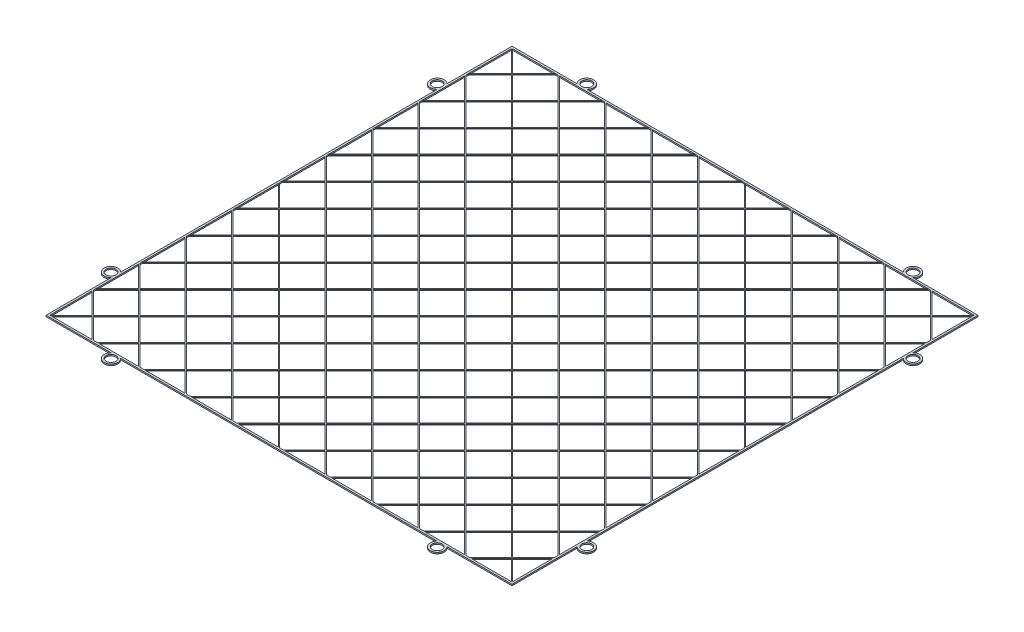
SolidWorks part; units mm, degrees
note: '?' marks a value the reader was unsure of.
ref_plane "Front" through (0, 0, 0) normal (0, 0, 1) x (1, 0, 0)
ref_plane "Top" through (0, 0, 0) normal (0, 1, 0) x (1, 0, 0)
ref_plane "Right" through (0, 0, 0) normal (1, 0, 0) x (0, 0, -1)
ref_axis "X" through (-80.9, 0, 0) along (1, 0, 0)?
ref_axis "Y" through (0, -50, 0) along (0, 1, 0)?
ref_axis "Z" through (0, 0, -80.9) along (0, 0, 1)?
sketch "Sketch1" plane through (0, 0, 0) normal (0, 1, 0) x (1, 0, 0)
  line L0 (-94.2, 94.2) -> (94.2, 94.2)
  line L1 (-95, 95) -> (95, 95)
  line L2 (-95, 95) -> (-95, -95)
  line L3 (-95, -95) -> (95, -95)
  line L4 (95, 95) -> (95, -95)
  line L5 (-95, 95) -> (95, -95) construction
  line L6 (-95, -95) -> (95, 95) construction
  line L7 (94.2, 94.2) -> (94.2, -94.2)
  line L8 (-94.2, -94.2) -> (94.2, -94.2)
  line L9 (-94.2, 94.2) -> (-94.2, -94.2)
  point P4 (0, 0)
  point P5 (0, 0)
  dimension "D1" = 190
  dimension "D2" = 0.8
extrude "Boss-Extrude1" add sketch "Sketch1" along normal mid plane 0.56
sketch "Sketch2" plane through (0, 0, 0) normal (0, 1, 0) x (1, 0, 0)
  line L0 (-79.1667, 95) -> (-79.1667, -95) construction
  line L1 (95, 95) -> (-95, 95) construction
  line L2 (-95, -95) -> (95, -95) construction
  line L3 (-95, 95) -> (-95, -95) construction
  line L4 (-79.3667, 95) -> (-79.3667, -95)
  line L5 (-78.9667, 95) -> (-78.9667, -95)
  line L6 (-79.3667, 95) -> (-78.9667, 95)
  line L7 (-79.3667, -95) -> (-78.9667, -95)
  dimension "D1" = 15.8333
  dimension "D2" = 0.2
  dimension "D3" = 0.2
ref_plane "Plane1" through (0, 0, 0) normal (0.7071, 0, -0.7071) x (-0.7071, 0, -0.7071)
ref_plane "Plane2" through (0, 0, 0) normal (-0.7071, 0, -0.7071) x (0, 1, 0)
sketch "Sketch4" plane through (0, 0, 0) normal (0.7071, 0, -0.7071) x (-0.7071, 0, -0.7071)
  line L1 (0.2, 0) -> (-0.2, 0)
  line L2 (0.2, 0) -> (0.2, -0.28)
  line L3 (0.2, -0.28) -> (-0.2, -0.28)
  line L4 (-0.2, 0) -> (-0.2, -0.28)
  line L5 (0.2, 0) -> (-0.2, -0.28) construction
  line L6 (0.2, -0.28) -> (-0.2, 0) construction
  point P4 (0, -0.14)
  point P5 (0, 0)
  point P7 (0, 0)
  dimension "D1" = 0.4
  dimension "D2" = 0.28
extrude "Boss-Extrude4" add sketch "Sketch4" along normal up to next and the other way up to next
pattern_linear "LPattern4" count 10 spacing 13.435 along (-0.7071, 0, -0.7071) count 10 spacing 13.435 along (0.7071, 0, 0.7071) of "Boss-Extrude4"
move or copy body "Body-Move/Copy2" bodies to move or copy 107 copy yes number of copies 1 rotation origin (0, 0, 0) rotation axis (0, 0, 1) rotation angle 180
sketch "Sketch5" plane through (0, 0, 0) normal (0, 1, 0) x (1, 0, 0)
  line L1 (-66.5, 85.7828) -> (-66.5, 97) construction
  line L2 (94.2, -74.9172) -> (-74.9172, 94.2) construction
  line L3 (-94.2, 58.0828) -> (-58.0828, 94.2) construction
  line L4 (-95, 95) -> (95, 95) construction
  line L5 (-74.9172, 94.2) -> (-56.4828, 94.2) construction
  circle A0 centre (-66.5, 97) radius 2
  circle A1 centre (-66.5, 97) radius 2.8
  point P3 (-66.5, 97.1719)
  dimension "D1" = 4
extrude "Boss-Extrude5" add sketch "Sketch5" along normal mid plane 0.56
mirror "Mirror2" about plane through (0, 0, 0) normal (1, 0, 0) of "Boss-Extrude5"
pattern_circular "CirPattern1" count 4 over 360 about axis through (0, 0, 0) along (0, 1, 0) of "Mirror2", "Boss-Extrude5"
